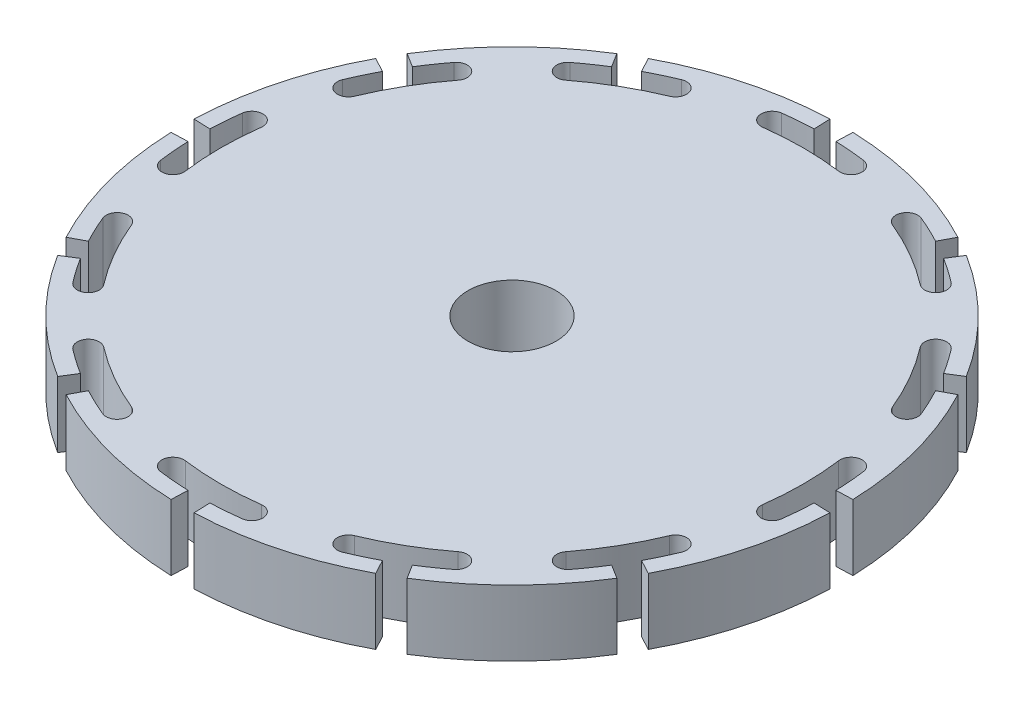
SolidWorks part; units mm, degrees
ref_plane "Front Plane" through (0, 0, 0) normal (0, 0, 1) x (1, 0, 0)
ref_plane "Top Plane" through (0, 0, 0) normal (0, 1, 0) x (1, 0, 0)
ref_plane "Right Plane" through (0, 0, 0) normal (1, 0, 0) x (0, 0, -1)
sketch "Sketch1" plane through (0, 0, 0) normal (0, 1, 0) x (1, 0, 0)
  circle A0 centre (0, 0) radius 30
  dimension "D1" = 60
sketch "Sketch2" plane through (0, 0, 0) normal (0, 1, 0) x (1, 0, 0)
  line L0 (0, 0) -> (0, 30) construction
  line L1 (-1.047, 29.9817) -> (0, 0) construction
  line L2 (0, 0) -> (-3.9158, 29.7433) construction
  line L3 (-1.047, 29.9817) -> (-0.9946, 28.4826)
  line L4 (0, 0) -> (3.9158, 29.7433) construction
  line L5 (1.047, 29.9817) -> (0, 0) construction
  line L6 (1.047, 29.9817) -> (0.9946, 28.4826)
  arc A0 (3.4589, 26.2733) -> (-3.4589, 26.2733) centre (0, 0) ccw
  circle A1 centre (0, 0) radius 30 construction
  arc A2 (-1.047, 29.9817) -> (1.047, 29.9817) centre (0, 0) cw
  arc A3 (-0.9946, 28.4826) -> (-3.72, 28.2562) centre (0, 0) ccw
  arc A4 (-3.4589, 26.2733) -> (-3.72, 28.2562) centre (-3.5895, 27.2647) cw
  arc A5 (3.4589, 26.2733) -> (3.72, 28.2562) centre (3.5895, 27.2647) ccw
  arc A6 (0.9946, 28.4826) -> (3.72, 28.2562) centre (0, 0) cw
  point P130 (0, 0)
  dimension "D1" = 15
  dimension "D2" = 2
  dimension "D4" = 1.5
  dimension "D3" = 4
sketch "Sketch3" plane through (0, 0, 0) normal (0, 1, 0) x (1, 0, 0)
  circle A0 centre (0, 0) radius 4
  dimension "D1" = 8
extrude "Wheel Blank" add sketch "Sketch1" along normal blind 6
extrude "T-Slot" cut sketch "Sketch2" along normal through all
pattern_circular "CirPattern1" count 12 over 360 about axis through (0, 6, 0) along (0, -1, 0) of "T-Slot"
extrude "Center Hole" cut sketch "Sketch3" along normal blind 6
